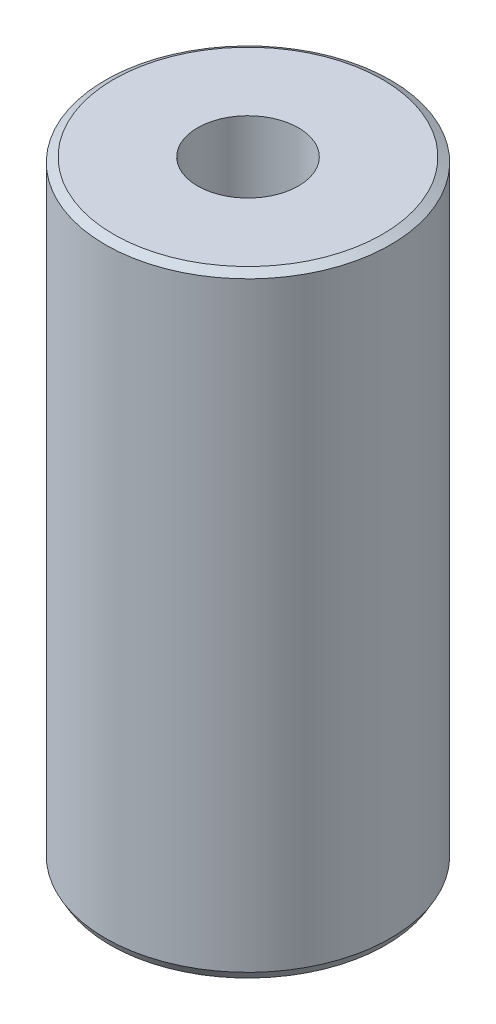
SolidWorks part; units mm, degrees
ref_plane "Front Plane" through (0, 0, 0) normal (0, 0, 1) x (1, 0, 0)
ref_plane "Top Plane" through (0, 0, 0) normal (0, 1, 0) x (1, 0, 0)
ref_plane "Right Plane" through (0, 0, 0) normal (1, 0, 0) x (0, 0, -1)
sketch "Sketch1" plane through (0, 0, 0) normal (0, 1, 0) x (1, 0, 0)
  circle A0 centre (0, 0) radius 60
  dimension "SHAFT_OD" = 120
extrude "Boss-Extrude1" add sketch "Sketch1" along normal blind 258.1799
sketch "Sketch2" plane through (0, 0, 0) normal (0, 1, 0) x (1, 0, 0)
  circle A0 centre (0, 0) radius 21.2244
  dimension "BORE_D" = 42.4487
extrude "Cut-Extrude1" cut sketch "Sketch2" along normal through all
chamfer "Chamfer1" distance 2.0194 angle 60 2 edges at (0, 258.1799, 60) (0, 0, 60) first distance on face at (0, 258.1799, 60) first distance on face at (0, 0, 21.2244)
